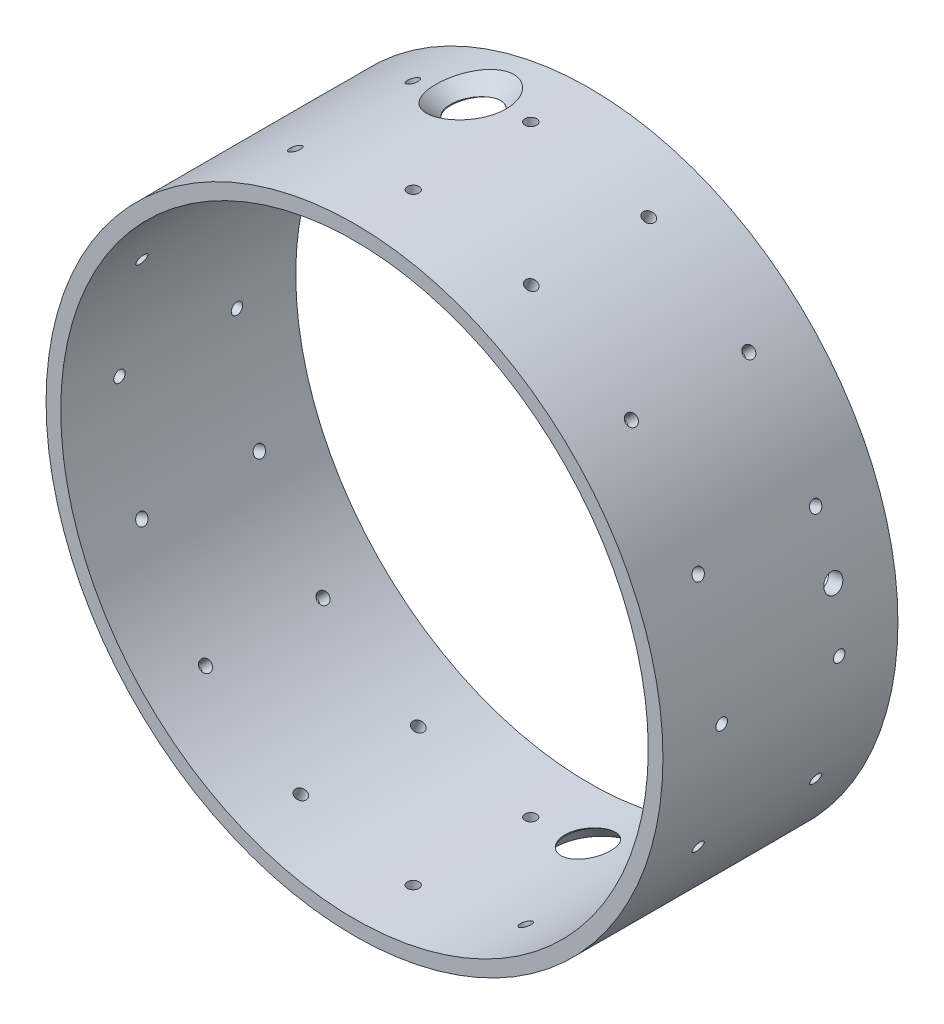
SolidWorks part; units mm, degrees
material "6061-T6 (SS)"
ref_plane "Front Plane" through (0, 0, 0) normal (0, 0, 1) x (1, 0, 0)
ref_plane "Top Plane" through (0, 0, 0) normal (0, 1, 0) x (1, 0, 0)
ref_plane "Right Plane" through (0, 0, 0) normal (1, 0, 0) x (0, 0, -1)
sketch "Sketch1" plane through (0, 0, 0) normal (0, 0, 1) x (1, 0, 0)
  circle A0 centre (0, 0) radius 63.5
  circle A1 centre (0, 0) radius 66.675
extrude "Extrude1" add sketch "Sketch1" along normal blind 50.8
ref_plane "Plane1" through (0, 0, 12.7) normal (0, 0, -1) x (-1, 0, 0)
sketch "Sketch2" plane through (0, 0, 12.7) normal (0, 0, -1) x (-1, 0, 0)
  line L0 (0, 0) -> (0, 66.675) construction
  line L1 (0, 0) -> (13.0076, 65.3939) construction
  line L2 (0, 0) -> (-65.3939, 13.0076) construction
  circle A0 centre (0, 0) radius 66.675 construction
  dimension "D1" = 11.25
  dimension "D2" = 90
ref_plane "Plane4" through (0, 66.675, 12.7) normal (0, 1, 0) x (-1, 0, 0)
sketch "Sketch7" plane through (0, 66.675, 12.7) normal (0, 1, 0) x (-1, 0, 0)
  line L0 (0, 0) -> (0, 25.4) construction
hole_wizard "#40 (0.098) Diameter Hole2" positions "Sketch9" profile "Sketch8" hole size "#40" standard "Ansi Inch"
sketch "Sketch9" plane through (0, 66.675, 12.7) normal (0, 1, 0) x (-1, 0, 0)
  point P1 (0, 0)
  point P4 (0, 25.4)
sketch "Sketch8" plane through (0, 66.675, 12.7) normal (1, 0, 0) x (0, 0, 1)
  line L0 (0, 0) -> (0, 13.4478)
  line L1 (0, 13.4478) -> (1.2446, 12.7)
  line L2 (1.2446, 12.7) -> (1.2446, 0)
  line L5 (1.2446, 0) -> (0, 0)
  line L10 (0, 13.4478) -> (-1.2446, 12.7) construction
  line L11 (0, -6.35) -> (0, 107.95) construction
  dimension "Hole Dia." = 2.4892
  dimension "Hole Depth" = 12.7
  dimension "Drill Angle" = 118
pattern_circular "CirPattern1" count 16 over 360 about axis through (0, 0, 50.8) along (0, 0, -1) of "#40 (0.098) Diameter Hole2"
ref_plane "Plane5" through (-13.0076, 65.3939, 12.7) normal (-0.1951, 0.9808, 0) x (-0.9808, -0.1951, 0)
hole_wizard "3/8 Clearance Hole1" positions "Sketch13" profile "Sketch14" hole size "3/8" standard "Ansi Inch"
sketch "Sketch13" plane through (-13.0076, 65.3939, 12.7) normal (-0.1951, 0.9808, 0) x (-0.9808, -0.1951, 0)
  point P1 (0, 0)
sketch "Sketch14" plane through (-13.0076, 65.3939, 12.7) normal (0, 0, 1) x (-0.9808, -0.1951, 0)
  line L0 (0, 0) -> (0, 15.9835)
  line L1 (0, 15.9835) -> (5.0419, 12.954)
  line L2 (5.0419, 12.954) -> (5.0419, 3.175)
  line L3 (5.0419, 3.175) -> (8.2169, 0)
  line L5 (8.2169, 0) -> (0, 0)
  line L6 (-5.0419, 3.175) -> (-8.2169, 0) construction
  line L10 (0, 15.9835) -> (-5.0419, 12.954) construction
  line L11 (0, -6.35) -> (0, 107.95) construction
  dimension "Hole Dia." = 10.0838
  dimension "Hole Depth" = 12.954
  dimension "Near C'Sink Dia." = 16.4338
  dimension "Near C'Sink Angle" = 90
  dimension "Drill Angle" = 118
ref_plane "Plane6" through (0, 0, 12.7) normal (-0.1951, 0.9808, 0) x (-0.9808, -0.1951, 0)
mirror "Mirror1" about plane through (0, 0, 12.7) normal (-0.1951, 0.9808, 0) of "3/8 Clearance Hole1"
ref_plane "Plane7" through (65.3939, 13.0076, 12.7) normal (0.9808, 0.1951, 0) x (0, 0, -1)
hole_wizard "#10-32 Tapped Hole1" positions "Sketch16" profile "Sketch15" tap size "#10-32" standard "Ansi Inch"
sketch "Sketch16" plane through (65.3939, 13.0076, 12.7) normal (0.9808, 0.1951, 0) x (0, 0, -1)
  point P1 (0, 0)
sketch "Sketch15" plane through (65.3939, 13.0076, 12.7) normal (0, 0, 1) x (-0.1951, 0.9808, 0)
  line L0 (0, 0) -> (0, 14.9293)
  line L1 (0, 14.9293) -> (2.0193, 13.716)
  line L2 (2.0193, 13.716) -> (2.0193, 0)
  line L5 (2.0193, 0) -> (0, 0)
  line L10 (0, 14.9293) -> (-2.0193, 13.716) construction
  line L11 (0, -6.35) -> (0, 107.95) construction
  dimension "Tap Drill Dia." = 4.0386
  dimension "Tap Drill Depth" = 13.716
  dimension "Drill Angle" = 118
cosmetic thread "Hole Thread1" parameters "D1"=3.2071, "D2"=4.826
